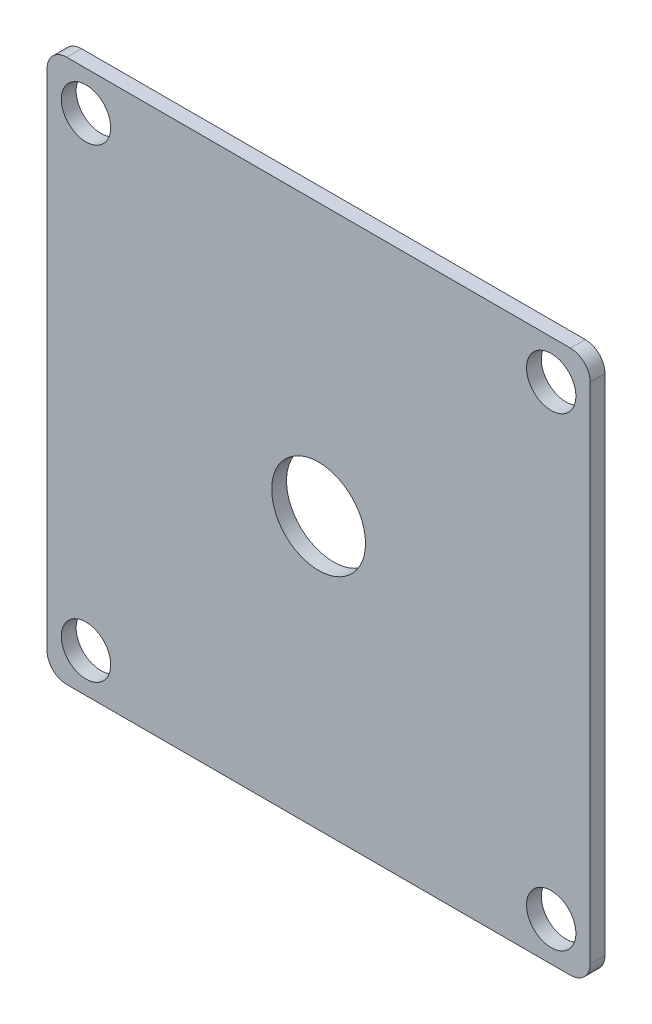
SolidWorks part; units mm, degrees
ref_plane "Спереди" through (0, 0, 0) normal (0, 0, 1) x (1, 0, 0)
ref_plane "Сверху" through (0, 0, 0) normal (0, 1, 0) x (1, 0, 0)
ref_plane "Справа" through (0, 0, 0) normal (1, 0, 0) x (0, 0, -1)
other "Configuration Table"
sketch "Эскиз1" plane through (0, 0, 0) normal (0, 0, 1) x (1, 0, 0)
  line L1 (2, 0) -> (53, 0)
  line L2 (0, 2) -> (0, 53)
  line L3 (2, 55) -> (53, 55)
  line L4 (55, 2) -> (55, 53)
  arc A0 (2, 0) -> (0, 2) centre (2, 2) cw
  arc A1 (53, 0) -> (55, 2) centre (53, 2) ccw
  arc A2 (53, 55) -> (55, 53) centre (53, 53) cw
  arc A3 (0, 53) -> (2, 55) centre (2, 53) cw
  point P7 (0, 0)
  point P10 (55, 0)
  point P13 (55, 55)
  point P16 (0, 55)
  dimension "D3" = 2
  dimension "D1" = 55
  dimension "D2" = 55
extrude "Бобышка-Вытянуть1" add sketch "Эскиз1" along normal blind 1.5
sketch "Эскиз2" plane through (0, 0, 1.5) normal (0, 0, 1) x (1, 0, 0)
  line L0 (0, 53) -> (0, 2) construction
  line L1 (53, 55) -> (2, 55) construction
  circle A0 centre (27.5, 27.5) radius 4.75
  point P4 (0, 27.5)
  point P7 (27.5, 55)
  dimension "D1" = 9.5
  dimension "D2" = 0
  dimension "D3" = 0
extrude "Вырез-Вытянуть1" cut sketch "Эскиз2" against normal through all
sketch "Эскиз3" plane through (0, 0, 1.5) normal (0, 0, 1) x (1, 0, 0)
  circle A0 centre (3.95, 3.95) radius 2.5
  circle A1 centre (27.5, 27.5) radius 4.75 construction
  circle A2 centre (51.05, 3.95) radius 2.5
  circle A3 centre (51.05, 51.05) radius 2.5
  circle A4 centre (3.95, 51.05) radius 2.5
  dimension "D3" = 5
  dimension "D1" = 23.55
  dimension "D2" = 23.55
  dimension "D4" = 2
  dimension "D5" = 2
extrude "Вырез-Вытянуть2" cut sketch "Эскиз3" against normal through all
